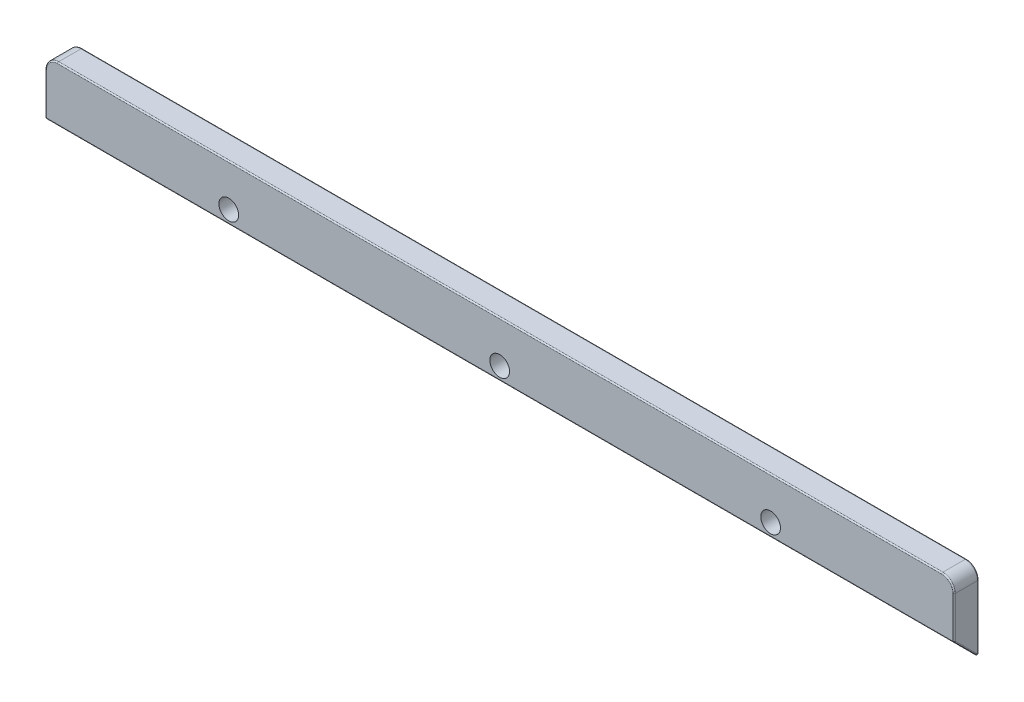
SolidWorks part; units mm, degrees
material "6061-T6 (SS)"
ref_plane "Front Plane" through (0, 0, 0) normal (0, 0, 1) x (1, 0, 0)
ref_plane "Top Plane" through (0, 0, 0) normal (0, 1, 0) x (1, 0, 0)
ref_plane "Right Plane" through (0, 0, 0) normal (1, 0, 0) x (0, 0, -1)
sketch "Sketch1" plane through (0, 0, 0) normal (1, 0, 0) x (0, 0, -1)
  line L0 (-3.0983, 0) -> (1.226, 0) construction
  line L1 (0, -3.2) -> (-2, -1.2)
  line L2 (0, -3.2) -> (0, 3.2)
  line L4 (-2, -1.2) -> (-2, 3.2)
  line L5 (-2, 3.2) -> (0, 3.2)
  dimension "D1" = 2
  dimension "D2" = 45
  dimension "D3" = 6.4
extrude "Boss-Extrude1" add sketch "Sketch1" along normal mid plane 73.8
fillet "Fillet1" radius 0.1 10 edges at (0, 3.2, 0) (0, 3.2, 2) (0, -3.2, 0) (0, -1.2, 2) (36.9, 1, 2) (36.9, 0, 0) (36.9, -2.2, 1) (-36.9, 1, 2) (-36.9, -2.2, 1) (-36.9, 0, 0)
sketch "Sketch4" [suppressed] plane through (0, 0, 0) normal (0, 0, 1) x (1, 0, 0)
  line L1 (7.5, 1.5) -> (-7.5, 1.5)
  line L2 (7.5, 1.5) -> (7.5, -3.2)
  line L3 (7.5, -3.2) -> (-7.5, -3.2)
  line L4 (-7.5, 1.5) -> (-7.5, -3.2)
  line L5 (0, 7.7759) -> (0, -8.8374) construction
  line L8 (-7.5, -3.2) -> (-7.5, 0.8) construction
  dimension "D1" = 4.7
hole_wizard "M2x0.4 Tapped Hole1" positions "Sketch2" profile "Sketch3" tap size "M2x0.4" standard "ANSI Metric" end condition through all
sketch "Sketch2" plane through (0, 0, 2) normal (0, 0, 1) x (1, 0, 0)
  circle A0 centre (-22, -0.2) radius 1.2
  circle A1 centre (-22, -0.2) radius 1.2 construction
  circle A2 centre (22, -0.2) radius 1.2
  circle A3 centre (22, -0.2) radius 1.2 construction
  point P0 (22, -0.2)
  point P2 (0, -0.2)
  point P5 (-22, -0.2)
sketch "Sketch3" plane through (22, -0.2, 2) normal (1, 0, 0) x (0, -1, 0)
  line L0 (0, 0) -> (0, 2)
  line L1 (0, 2) -> (0.8, 2)
  line L2 (0.8, 2) -> (0.8, 0)
  line L5 (0.8, 0) -> (0, 0)
  line L11 (0, -6.35) -> (0, 107.95) construction
  dimension "Thru Tap Drill Dia." = 1.6
  dimension "Thru Tap Drill Depth" = 2
cosmetic thread "Hole Thread1" parameters "D2"=2
cosmetic thread "Hole Thread2" parameters "D2"=2
cosmetic thread "Hole Thread3" parameters "D2"=2
extrude "Cut-Extrude4" [suppressed] cut sketch "Sketch4" along normal through all
fillet "Fillet2" [suppressed] radius 0.2
fillet "Fillet3" radius 1 6 edges at (36.8707, 3.1707, 1.9707) (36.8707, 3.1707, 0.0293) (-36.8707, 3.1707, 1.9707) (-36.8707, 3.1707, 0.0293) (-36.9, 3.2, 1) (36.9, 3.2, 1)
